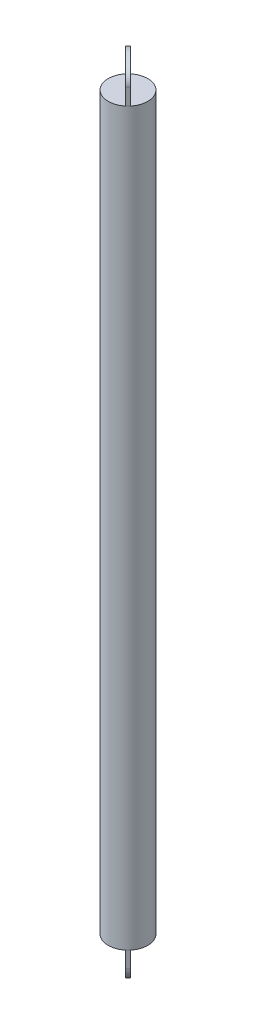
SolidWorks part; units mm, degrees
ref_plane "Front Plane" through (0, 0, 0) normal (0, 0, 1) x (1, 0, 0)
ref_plane "Top Plane" through (0, 0, 0) normal (0, 1, 0) x (1, 0, 0)
ref_plane "Right Plane" through (0, 0, 0) normal (1, 0, 0) x (0, 0, -1)
sketch "Sketch1" plane through (0, 0, 0) normal (0, 1, 0) x (1, 0, 0)
  circle A0 centre (0, 0) radius 6
  dimension "D1" = 12
extrude "Boss-Extrude2" add sketch "Sketch1" along normal blind 111
ref_plane "Plane1" through (0, 0, 0) normal (0.7071, 0, -0.7071) x (-0.7071, 0, -0.7071)
sketch "Sketch4" plane through (0, 0, 0) normal (0.7071, 0, -0.7071) x (-0.7071, 0, -0.7071)
  line L0 (6, 0) -> (6, -10) construction
  line L1 (0, 0) -> (0, -10) construction
  line L2 (5, -5) -> (5, 0)
  line L3 (5, 0) -> (6, 0)
  line L4 (6, 0) -> (6, -5)
  line L5 (-5, 0) -> (-6, 0)
  line L6 (-5, -5) -> (-5, 0)
  line L7 (-6, 0) -> (-6, -5)
  ellipse E0 centre (0, -5) end of major axis (6, -5) minor radius 5 (6, -5) -> (-6, -5) cw
  ellipse E1 centre (0, -5) end of major axis (5, -5) minor radius 4 (5, -5) -> (-5, -5) cw
  dimension "D1" = 10
  dimension "D4" = 5
extrude "Boss-Extrude4" add sketch "Sketch4" along normal blind 0.5 and the other way blind 0.5
mirror "Mirror1" about plane through (0, 111, 0) normal (0, 1, 0) of "Boss-Extrude4", "Boss-Extrude2"
